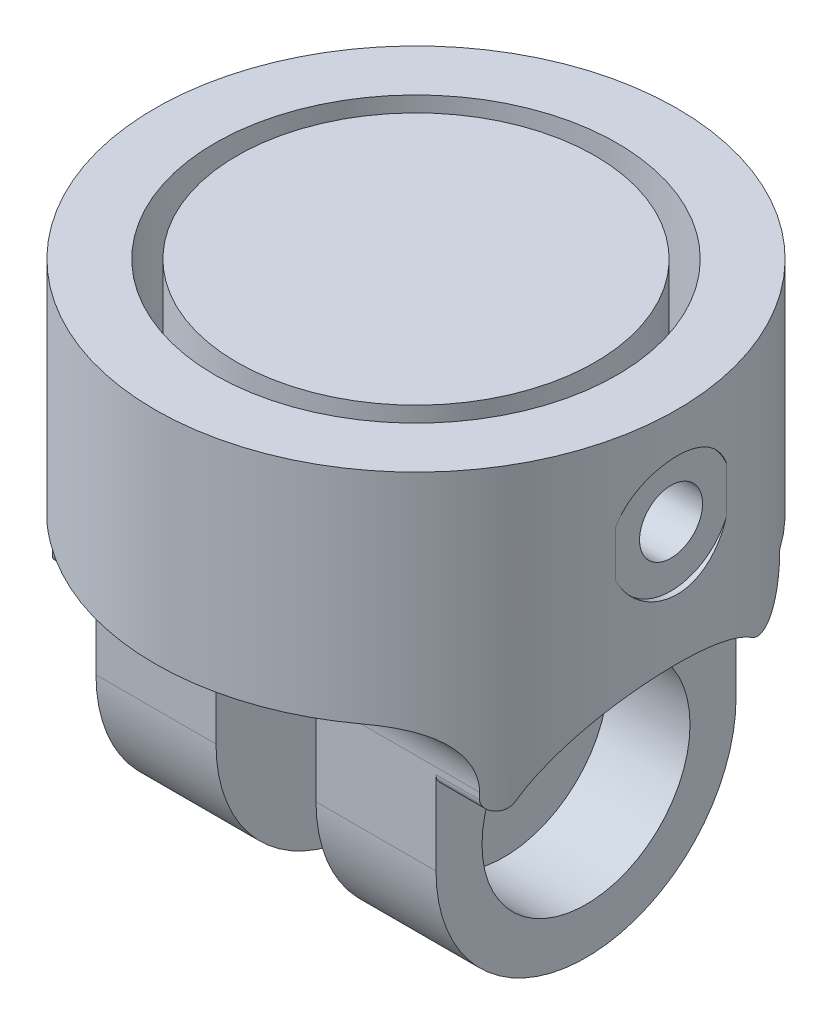
SolidWorks part; units mm, degrees
material "PLA Black"
ref_plane "Front" through (0, 0, 0) normal (0, 0, 1) x (1, 0, 0)
ref_plane "Top" through (0, 0, 0) normal (0, 1, 0) x (1, 0, 0)
ref_plane "Right" through (0, 0, 0) normal (1, 0, 0) x (0, 0, -1)
sketch "Sketch1" plane through (0, 0, 0) normal (0, 1, 0) x (1, 0, 0)
  line L0 (0, 8.95) -> (0, 10.05) construction
  circle A0 centre (0, 0) radius 10.05
  circle A1 centre (0, 0) radius 13.05
  circle A2 centre (0, 0) radius 9.5 construction
  circle A4 centre (0, 0) radius 8.95
  point P11 (0, 9.5)
  dimension "D1" = 1.1
  dimension "D2" = 3
  dimension "D3" = 19
extrude "Boss-Extrude1" add sketch "Sketch1" along normal blind 10 contours A1 A0 | A4 region at (-12.6809, 0, 0) region at (0, 0, 0)
sketch "Sketch3" plane through (0, 0, 0) normal (0, -1, 0) x (1, 0, 0)
  circle A2 centre (0, 0) radius 13.05 construction
  circle A3 centre (0, 0) radius 13.05
extrude "Boss-Extrude2" add sketch "Sketch3" along normal blind 1
sketch "Sketch4" plane through (0, -1, 0) normal (0, -1, 0) x (1, 0, 0)
  line L0 (0, 17.8908) -> (0, -17.0763) construction
  line L1 (2.5, 7.5) -> (8.5, 7.5)
  line L2 (2.5, 7.5) -> (2.5, -7.5)
  line L3 (2.5, -7.5) -> (8.5, -7.5)
  line L4 (8.5, 7.5) -> (8.5, -7.5)
  line L5 (-8.5, 7.5) -> (-8.5, -7.5)
  line L6 (-2.5, -7.5) -> (-8.5, -7.5)
  line L7 (-2.5, 7.5) -> (-2.5, -7.5)
  line L8 (-2.5, 7.5) -> (-8.5, 7.5)
  line L9 (16.8049, 0) -> (-19.8998, 0) construction
  dimension "D1" = 6
  dimension "D2" = 5
  dimension "D3" = 15
extrude "Boss-Extrude3" add sketch "Sketch4" along normal blind 15
sketch "Sketch5" plane through (8.5, 0, 0) normal (1, 0, 0) x (0, 0, -1)
  line L0 (-7.5, -16) -> (-7.5, -1) construction
  line L1 (7.5, -16) -> (7.5, -1) construction
  line L2 (7.5, -8.5) -> (7.5, -17.1619)
  line L3 (7.5, -17.1619) -> (-7.5, -17.1619)
  line L4 (-7.5, -17.1619) -> (-7.5, -8.5)
  arc A0 (-7.5, -8.5) -> (7.5, -8.5) centre (0, -8.5) ccw
  circle A1 centre (0, -8.5) radius 1.55
  dimension "D1" = 3.1
extrude "Cut-Extrude1" cut sketch "Sketch5" against normal through all both and the other way through all
sketch "Sketch6" plane through (8.5, 0, 0) normal (1, 0, 0) x (0, 0, -1)
  circle A0 centre (0, -8.5) radius 5.2
  dimension "D1" = 10.4
extrude "Cut-Extrude2" cut sketch "Sketch6" against normal blind 4.1
mirror "Mirror1" about plane through (0, 0, 0) normal (1, 0, 0) of "Cut-Extrude2"
ref_plane "Plane9" through (1.335, 0, 0) normal (1, 0, 0) x (0, 0, -1)
sketch "Sketch7" plane through (1.335, 0, 0) normal (1, 0, 0) x (0, 0, -1)
  line L0 (3.555, -8.5) -> (3.555, -1) construction
  line L1 (7.5, -1) -> (-7.5, -1) construction
  line L2 (3.4474, -7.632) -> (1.7775, -1) construction
  line L3 (3.1303, -6.8149) -> (0, -1) construction
  line L4 (1.7775, -0.6757) -> (1.7775, -1.4422) construction
  line L5 (2.6911, -6.1771) -> (-1.7775, -1) construction
  line L6 (2.2506, -5.7481) -> (-3.555, -1) construction
  line L8 (0, -1.6788) -> (0, 0) construction
  line L9 (-8.4824, -8.5) -> (8.712, -8.5) construction
  line L10 (1.8766, -5.4807) -> (-5.3325, -1) construction
  line L11 (-3.555, -0.3587) -> (-3.555, -1.6788) construction
  circle A0 centre (0, -8.5) radius 3.555 construction
  dimension "D1" = 7.11
  dimension "D2" = 31.862
  dimension "D3" = 7.5
ref_plane "Plane1" through (1.335, -1, -3.555) normal (0, 1, 0) x (1, 0, 0)
ref_plane "Plane2" through (1.335, -1, -1.7775) normal (0, 0.9697, 0.2442) x (1, 0, 0)
ref_plane "Plane3" through (1.335, -1, 0) normal (0, 0.8805, 0.474) x (1, 0, 0)
ref_plane "Plane5" through (1.335, -1, 1.7775) normal (0, 0.757, 0.6534) x (1, 0, 0)
ref_plane "Plane6" through (1.335, -1, 3.555) normal (0, 0.6331, 0.7741) x (1, 0, 0)
ref_plane "Plane7" through (1.335, -1, 5.3325) normal (0, 0.5279, 0.8493) x (1, 0, 0)
sketch "Sketch8" plane through (1.335, -1, -3.555) normal (0, 1, 0) x (1, 0, 0)
  circle A0 centre (0, 0) radius 0.4895
  dimension "D1" = 0.979
extrude "Cut-Extrude5" cut sketch "Sketch8" along normal blind 5.5 and the other way through all
sketch "Sketch9" plane through (1.335, -1, -1.7775) normal (0, 0.9697, 0.2442) x (1, 0, 0)
  circle A0 centre (0, 0) radius 0.4895
  dimension "D1" = 0.979
extrude "Cut-Extrude3" cut sketch "Sketch9" along normal blind 5.5
sketch "Sketch10" plane through (1.335, -1, 0) normal (0, 0.8805, 0.474) x (1, 0, 0)
  circle A0 centre (0, 0) radius 0.4895
  dimension "D1" = 0.979
sketch "Sketch11" plane through (1.335, -1, 1.7775) normal (0, 0.757, 0.6534) x (1, 0, 0)
  circle A0 centre (0, 0) radius 0.4895
  dimension "D1" = 0.979
sketch "Sketch12" plane through (1.335, -1, 3.555) normal (0, 0.6331, 0.7741) x (1, 0, 0)
  circle A0 centre (0, 0) radius 0.4895
  dimension "D1" = 0.979
sketch "Sketch14" plane through (1.335, -1, 5.3325) normal (0, 0.5279, 0.8493) x (1, 0, 0)
  circle A0 centre (0, 0) radius 0.4895
  dimension "D1" = 0.979
extrude "Cut-Extrude6" cut sketch "Sketch10" along normal blind 5.5 and the other way through all
extrude "Cut-Extrude7" cut sketch "Sketch11" along normal blind 5.5 and the other way through all contours A0
extrude "Cut-Extrude8" cut sketch "Sketch12" along normal blind 5.5 and the other way through all contours A0
extrude "Cut-Extrude9" cut sketch "Sketch14" along normal blind 5.5 and the other way through all contours A0
ref_plane "Plane8" through (13.05, 0, 0) normal (1, 0, 0) x (0, 0, -1)
hole_wizard "Tap Drill for M3 Helicoil1" positions "Sketch17" profile "Sketch18" hole size "M3x0.5" standard "DIN"
sketch "Sketch17" plane through (13.05, 0, 0) normal (1, 0, 0) x (0, 0, -1)
  line L0 (-22.2973, 5) -> (18.0703, 5) construction
  line L4 (0, 12.2732) -> (0, -5.3405) construction
  line L6 (-7.5, -8.5) -> (-7.5, -1) construction
  line L7 (7.5, -8.5) -> (7.5, -1) construction
  line L8 (13.05, 10) -> (-13.05, 10) construction
  line L9 (10.05, 0) -> (-10.05, 0) construction
  point P0 (0, 5)
sketch "Sketch18" plane through (13.05, 5, 0) normal (0, 1, 0) x (0, 0, -1)
  line L0 (0, 0) -> (0, 6.9464)
  line L1 (0, 6.9464) -> (1.575, 6)
  line L2 (1.575, 6) -> (1.575, 0)
  line L5 (1.575, 0) -> (0, 0)
  line L10 (0, 6.9464) -> (-1.575, 6) construction
  line L11 (0, -6.35) -> (0, 107.95) construction
  dimension "Hole Dia." = 3.15
  dimension "Hole Depth" = 6
  dimension "Drill Angle" = 118
sketch "Sketch20" plane through (13.05, 0, 0) normal (1, 0, 0) x (0, 0, -1)
  circle A0 centre (0, 5) radius 3
  dimension "D1" = 6
extrude "Cut-Extrude10" cut sketch "Sketch20" against normal blind 0.3
sketch "Sketch21" plane through (8.5, 0, 0) normal (1, 0, 0) x (0, 0, -1)
  line L0 (7.5, -1) -> (-7.5, -1) construction
  line L1 (7.5, -0.1252) -> (7.5, -1.1767)
  line L2 (0.9244, -19.0662) -> (-4.8209, -14.2453) construction
  line L3 (0, 5.2718) -> (0, -9.2894) construction
  line L4 (0, 10) -> (0, -1) construction
  line L5 (-7.5, -0.1252) -> (-7.5, -4.3226)
  line L6 (7.5, -0.1252) -> (-7.5, -0.1252)
  line L7 (-7.5, -8.5) -> (-7.5, -1) construction
  line L8 (7.5, -8.5) -> (7.5, -1) construction
  line L9 (0, -1) -> (9.4693, -4.4465) construction
  line L10 (0, -1) -> (1.6171, -0.0664) construction
  line L11 (4.6128, -2.5863) -> (7.5, -1.1767) construction
  line L12 (10.5662, -7.5756) -> (4.8209, -2.7547) construction
  line L13 (-4.8209, -14.2453) -> (4.8209, -2.7547) construction
  line L14 (10.5662, -7.5756) -> (0.9244, -19.0662) construction
  arc A0 (-6.4204, -4.6233) -> (4.6128, -2.5863) centre (0, -8.5) cw
  arc A1 (-6.4204, -4.6233) -> (-7.5, -4.3226) centre (-6.9183, -4.3226) cw
  arc A2 (7.5, -1.1767) -> (4.6128, -2.5863) centre (5.7123, -1.1767) cw
  circle A3 centre (0, -8.5) radius 1.55 construction
  arc A4 (-4.8209, -14.2453) -> (4.8209, -2.7547) centre (0, -8.5) cw construction
  dimension "D1" = 30
  dimension "D3" = 7.5
  dimension "D2" = 50
  dimension "D4" = 15
extrude "Boss-Extrude4" add sketch "Sketch21" along normal up to surface (2.1795 mm away) up to face at (12.895, 5, 0)
mirror "Mirror2" about plane through (0, 0, 0) normal (1, 0, 0) of "Boss-Extrude4", "Tap Drill for M3 Helicoil1", "Cut-Extrude10"
fillet "Fillet1" radius 3 2 edges at (-6.5898, -1, 7.5) (6.5898, -1, 7.5)
equation "\"knee_angle\"= 0"
equation "\"ankle_angle\" = 90"
equation "\"hip_angle\" = 30"
equation "\"spring_ankle_parallel_arm_diameter\"= 0.89"
equation "\"spring_ankle_parallel_arm_length\"= 13"
equation "\"spring_ankle_parallel_intern_diameter\"= 6.22"
equation "\"spring_ankle_parallel_angle\"= \"ankle_angle\""
equation "\"spring_ankle_parallel_turns\"= 3"
equation "\"spring_ankle_parallel_pitch\"= \"spring_ankle_parallel_arm_diameter\" * 1.01"
equation "\"spring_ankle_parallel_cutting_distance\"= (1-\"spring_ankle_parallel_angle\" / 360) * \"spring_ankle_parallel_pitch\""
equation "\"spring_ankle_serial_arm_diameter\"= 0.89"
equation "\"spring_ankle_serial_arm_length\"= 10"
equation "\"spring_ankle_serial_intern_diameter\"= 6.22"
equation "\"spring_ankle_serial_angle\"= \"90\""
equation "\"spring_ankle_serial_turns\"= 3"
equation "\"spring_ankle_serial_pitch\"= \"spring_ankle_serial_arm_diameter\" * 1.01"
equation "\"spring_ankle_serial_cutting_distance\"= (1-\"spring_ankle_serial_angle\" / 360) * \"spring_ankle_serial_pitch\""
equation "\"spring_knee_parallel_arm_diameter\"= 0.89"
equation "\"spring_knee_parallel_arm_length\"= 15"
equation "\"spring_knee_parallel_intern_diameter\"= 5.46"
equation "\"spring_knee_parallel_angle\"= -\"knee_angle\" + 90"
equation "\"spring_knee_parallel_turns\"= 3"
equation "\"spring_knee_parallel_pitch\"= \"spring_knee_parallel_arm_diameter\" * 1.01"
equation "\"spring_knee_parallel_cutting_distance\"= (1-(\"spring_knee_parallel_angle\") / 360) * \"spring_knee_parallel_pitch\""
equation "\"spring_knee_serial_arm_diameter\"= 0.89"
equation "\"spring_knee_serial_arm_length\"= 10"
equation "\"spring_knee_serial_intern_diameter\"= 5.46"
equation "\"spring_knee_serial_angle\"= \"90\""
equation "\"spring_knee_serial_turns\"= 3"
equation "\"spring_knee_serial_pitch\"= \"spring_knee_serial_arm_diameter\" * 1.01"
equation "\"spring_knee_serial_cutting_distance\"= (1-\"spring_knee_serial_angle\" / 360) * \"spring_knee_serial_pitch\""
equation "\"spring_ankle_parallel_nominal_diameter\"= \"spring_ankle_parallel_arm_diameter\" + \"spring_ankle_parallel_intern_diameter\""
equation "\"spring_ankle_serial_nominal_diameter\"= \"spring_ankle_serial_arm_diameter\" + \"spring_ankle_serial_intern_diameter\""
equation "\"spring_knee_parallel_nominal_diameter\"= \"spring_knee_parallel_arm_diameter\" + \"spring_knee_parallel_intern_diameter\""
equation "\"spring_knee_serial_nominal_diameter\"= \"spring_knee_serial_arm_diameter\" + \"spring_knee_serial_intern_diameter\""
equation "\"D1@Sketch7\"=\"spring_ankle_parallel_nominal_diameter\""
equation "\"D1@Sketch8\"=\"spring_ankle_parallel_arm_diameter\"*1.1"
equation "\"D1@Sketch9\"=\"spring_ankle_parallel_arm_diameter\"*1.1"
equation "\"D1@Sketch10\"=\"spring_ankle_parallel_arm_diameter\"*1.1"
equation "\"D1@Sketch11\"=\"spring_ankle_parallel_arm_diameter\"*1.1"
equation "\"D1@Sketch12\"=\"spring_ankle_parallel_arm_diameter\"*1.1"
equation "\"D1@Sketch14\"=\"spring_ankle_parallel_arm_diameter\"*1.1"
equation "\"D1@Cut-Extrude3\"=\"spring_ankle_parallel_arm_length\"-\"axis_structure_distance\""
equation "\"axis_structure_distance\"= 7.5"
equation "\"D1@Cut-Extrude5\"=\"spring_ankle_parallel_arm_length\"-\"axis_structure_distance\""
equation "\"D1@Cut-Extrude6\"=\"spring_ankle_parallel_arm_length\"-\"axis_structure_distance\""
equation "\"D1@Cut-Extrude7\"=\"spring_ankle_parallel_arm_length\"-\"axis_structure_distance\""
equation "\"D1@Cut-Extrude8\"=\"spring_ankle_parallel_arm_length\"-\"axis_structure_distance\""
equation "\"D1@Cut-Extrude9\"=\"spring_ankle_parallel_arm_length\"-\"axis_structure_distance\""
equation "\"D1@Boss-Extrude3\"=\"axis_structure_distance\"*2"
equation "\"ankle_angle_max\" = 120"
equation "\"ankle_angle_min\" = 50"
equation "\"knee_angle_max\" = 120"
equation "\"knee_angle_min\" = 0"
equation "\"hip_angle_max\" = 45"
equation "\"hip_angle_min\" = -45"
equation "\"D1@Sketch21\"=\"ankle_angle_max\"-90"
equation "\"D2@Sketch21\"=\"ankle_angle_min\""
equation "\"D1@Plane9\"=(\"spring_ankle_parallel_arm_diameter\"*\"spring_ankle_parallel_turns\")/2"
